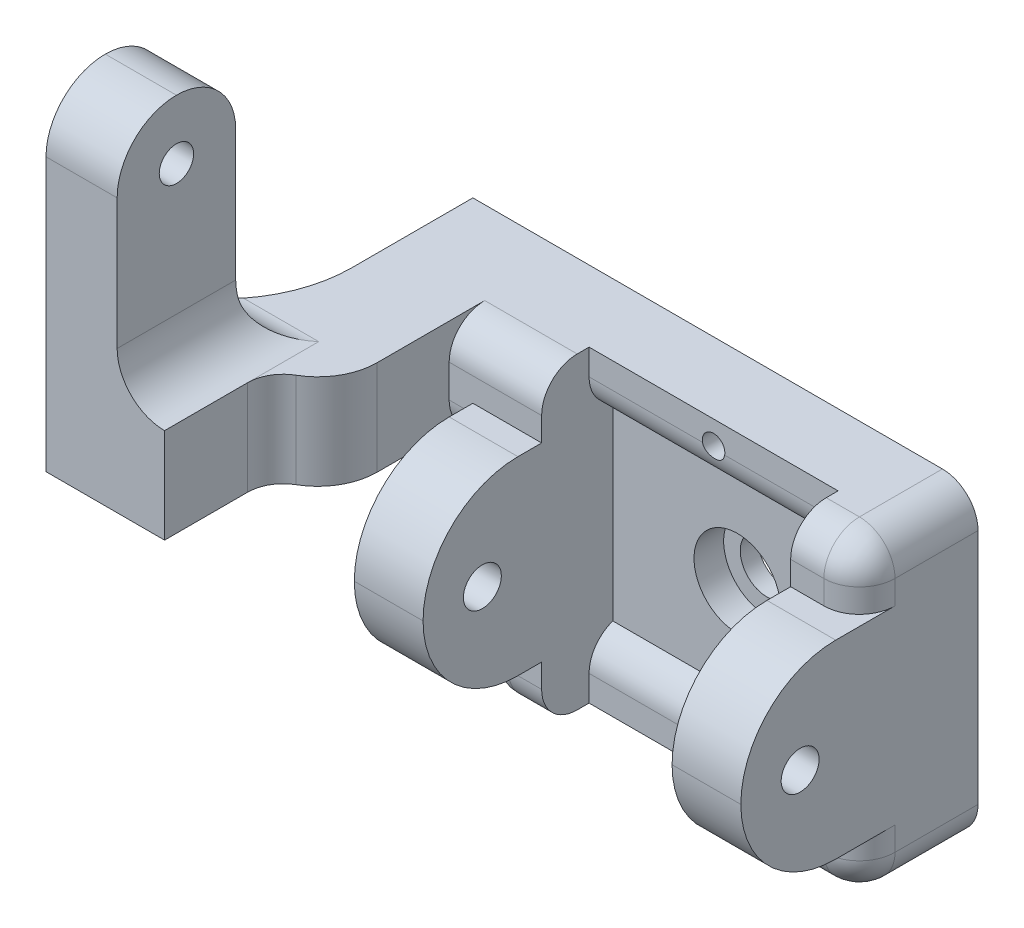
SolidWorks part; units mm, degrees
ref_plane "Front" through (0, 0, 0) normal (0, 0, 1) x (1, 0, 0)
ref_plane "Top" through (0, 0, 0) normal (0, 1, 0) x (1, 0, 0)
ref_plane "Right" through (0, 0, 0) normal (1, 0, 0) x (0, 0, -1)
sketch "Sketch1" plane through (0, 0, 0) normal (0, 0, 1) x (1, 0, 0)
  line L1 (0, 0) -> (-32.6, 0)
  line L2 (0, 0) -> (0, 26)
  line L3 (0, 26) -> (-32.6, 26)
  line L4 (-32.6, 0) -> (-32.6, 26)
  dimension "D1" = 32.6
  dimension "D2" = 26
extrude "Boss-Extrude1" add sketch "Sketch1" along normal blind 4
sketch "Sketch2" plane through (0, 0, 4) normal (0, 0, 1) x (1, 0, 0)
  line L0 (0, 26) -> (-32.6, 26) construction
  line L1 (0, 0) -> (0, 26) construction
  circle A0 centre (-16.3, 13) radius 3.65
  dimension "D1" = 7.3
  dimension "D2" = 13
  dimension "D3" = 16.3
extrude "Cut-Extrude1" cut sketch "Sketch2" against normal blind 2.5
sketch "Sketch3" plane through (0, 0, 1.5) normal (0, 0, 1) x (1, 0, 0)
  circle A0 centre (-16.3, 13) radius 2.25
  dimension "D1" = 4.5
extrude "Cut-Extrude2" cut sketch "Sketch3" against normal through all
sketch "Sketch4" plane through (0, 0, 4) normal (0, 0, 1) x (1, 0, 0)
  line L0 (-32.6, 0) -> (0, 0) construction
  line L1 (0, 26) -> (-5.8, 26)
  line L2 (0, 26) -> (0, 0)
  line L3 (0, 0) -> (-5.8, 0)
  line L4 (-5.8, 26) -> (-5.8, 0)
  line L6 (-32.6, 26) -> (-26.8, 26)
  line L7 (-32.6, 26) -> (-32.6, 0)
  line L8 (-32.6, 0) -> (-26.8, 0)
  line L9 (-26.8, 26) -> (-26.8, 0)
  dimension "D1" = 5.8
  dimension "D2" = 5.8
extrude "Boss-Extrude2" add sketch "Sketch4" along normal blind 16
sketch "Sketch5" plane through (0, 0, 0) normal (1, 0, 0) x (0, 0, -1)
  line L0 (-20, 0) -> (-20, 26) construction
  line L1 (-20, 0) -> (0, 0) construction
  circle A0 centre (-15, 13) radius 1.6
  dimension "D1" = 3.2
  dimension "D2" = 5
  dimension "D3" = 13
extrude "Cut-Extrude3" cut sketch "Sketch5" against normal through all
sketch "Sketch6" plane through (0, 0, 4) normal (0, 0, 1) x (1, 0, 0)
  line L1 (-26.8, 26) -> (-5.8, 26)
  line L2 (-26.8, 26) -> (-26.8, 21)
  line L3 (-26.8, 21) -> (-5.8, 21)
  line L4 (-5.8, 26) -> (-5.8, 21)
  line L5 (-26.8, 0) -> (-5.8, 0)
  line L6 (-26.8, 0) -> (-26.8, 5)
  line L7 (-26.8, 5) -> (-5.8, 5)
  line L8 (-5.8, 0) -> (-5.8, 5)
  dimension "D1" = 5
  dimension "D2" = 5
extrude "Boss-Extrude3" add sketch "Sketch6" along normal blind 2
sketch "Sketch7" plane through (-32.6, 0, 0) normal (-1, 0, 0) x (0, 0, 1)
  line L1 (20, 26) -> (10, 26)
  line L2 (20, 26) -> (20, 21)
  line L3 (20, 21) -> (10, 21)
  line L4 (10, 26) -> (10, 21)
  line L5 (20, 0) -> (10, 0)
  line L6 (20, 0) -> (20, 5)
  line L7 (20, 5) -> (10, 5)
  line L8 (10, 0) -> (10, 5)
  dimension "D1" = 10
  dimension "D2" = 10
  dimension "D3" = 5
  dimension "D4" = 5
extrude "Cut-Extrude4" cut sketch "Sketch7" against normal through all
fillet "Fillet1" radius 8 4 edges at (-2.9, 5, 20) (-2.9, 21, 20) (-29.7, 5, 20) (-29.7, 21, 20)
sketch "Sketch12" plane through (-32.6, 0, 0) normal (-1, 0, 0) x (0, 0, 1)
  line L0 (0, 26) -> (0, 0) construction
  line L1 (10, 26) -> (0, 26)
  line L2 (10, 26) -> (10, 18)
  line L3 (10, 18) -> (0, 18)
  line L4 (0, 26) -> (0, 18)
  dimension "D1" = 8
extrude "Boss-Extrude8" add sketch "Sketch12" along normal blind 10
sketch "Sketch13" plane through (0, 0, 10) normal (0, 0, 1) x (1, 0, 0)
  line L0 (-26.8, 26) -> (-42.6, 26) construction
  line L1 (-42.6, 18) -> (-34.6, 18)
  line L2 (-42.6, 18) -> (-42.6, 26)
  line L3 (-42.6, 26) -> (-34.6, 26)
  line L4 (-34.6, 18) -> (-34.6, 26)
  dimension "D1" = 8
extrude "Boss-Extrude9" add sketch "Sketch13" along normal blind 10
fillet "Fillet2" radius 3 4 edges at (-30.7, 26, 10) (-2.9, 26, 10) (-2.9, 0, 10) (-29.7, 0, 10)
sketch "Sketch14" plane through (0, 0, 20) normal (0, 0, 1) x (1, 0, 0)
  line L0 (-42.6, 18) -> (-34.6, 18) construction
  line L1 (-38.6, 18) -> (-48.6, 18)
  line L2 (-38.6, 18) -> (-38.6, 26)
  line L3 (-38.6, 26) -> (-48.6, 26)
  line L4 (-48.6, 18) -> (-48.6, 26)
  dimension "D1" = 8
  dimension "D2" = 10
extrude "Boss-Extrude10" add sketch "Sketch14" along normal blind 10
sketch "Sketch15" plane through (0, 26, 0) normal (0, 1, 0) x (1, 0, 0)
  line L1 (-48.6, -30) -> (-42.6, -30)
  line L2 (-48.6, -30) -> (-48.6, -20)
  line L3 (-48.6, -20) -> (-42.6, -20)
  line L4 (-42.6, -30) -> (-42.6, -20)
  dimension "D1" = 10
  dimension "D2" = 6
extrude "Boss-Extrude11" add sketch "Sketch15" along normal blind 20
fillet "Fillet10" radius 11 1 edges at (-42.6, 22, 20)
fillet "Fillet11" radius 3 1 edges at (-38.6, 22, 20)
fillet "Fillet12" radius 5 1 edges at (-34.6, 22, 20)
fillet "Fillet14" radius 4 1 edges at (-42.6, 26, 25)
fillet "Fillet15" radius 3 1 edges at (-43.6, 26, 20)
sketch "Sketch16" plane through (0, 0, 0) normal (0, 0, -1) x (-1, 0, 0)
  line L0 (42.6, 18) -> (32.6, 18)
  line L1 (32.6, 18) -> (32.6, 9)
  line L2 (32.6, 18) -> (32.6, 0) construction
  line L3 (32.6, 9) -> (42.6, 18)
  dimension "D1" = 9
extrude "Boss-Extrude12" add sketch "Sketch16" against normal blind 9
fillet "Fillet17" radius 3 1 edges at (-32.6, 9, 4.5)
fillet "Fillet18" radius 3 1 edges at (-33.6, 18, 10)
sketch "Sketch17" plane through (-48.6, 0, 0) normal (-1, 0, 0) x (0, 0, 1)
  line L0 (30, 46) -> (30, 18) construction
  line L1 (20, 46) -> (30, 46) construction
  circle A0 centre (25, 41) radius 1.45
  dimension "D1" = 2.9
  dimension "D2" = 5
  dimension "D3" = 5
extrude "Cut-Extrude5" cut sketch "Sketch17" against normal through all
fillet "Fillet19" radius 5 2 edges at (-45.6, 46, 20) (-45.6, 46, 30)
fillet "Fillet21" radius 3 2 edges at (-16.3, 21, 6) (-16.3, 5, 6)
fillet "Fillet22" radius 3 9 edges at (0, 22, 10) (0, 25.1213, 9.1213) (0, 4, 10) (0, 0.8787, 9.1213) (-32.6, 4, 10) (-32.6, 0.8787, 9.1213) (0, 26, 3.5) (0, 0, 3.5) (-32.6, 0, 3.5)
sketch "Sketch18" plane through (0, 0, 0) normal (0, 0, -1) x (-1, 0, 0)
  line L0 (29.6, 0) -> (3, 0) construction
  line L1 (3, 26) -> (42.6, 26) construction
  line L2 (0, 3) -> (0, 23) construction
  line L3 (32.6, 7.6639) -> (32.6, 3) construction
  circle A0 centre (16.3, 2) radius 0.95
  circle A1 centre (3.5, 13) radius 1.2
  circle A2 centre (29.1, 13) radius 1.2
  circle A3 centre (16.3, 24) radius 0.95
  dimension "D1" = 1.9
  dimension "D2" = 1.9
  dimension "D3" = 2.4
  dimension "D4" = 2.4
  dimension "D5" = 2
  dimension "D6" = 2
  dimension "D7" = 3.5
  dimension "D8" = 3.5
  dimension "D9" = 13
extrude "Cut-Extrude6" cut sketch "Sketch18" against normal blind 8
